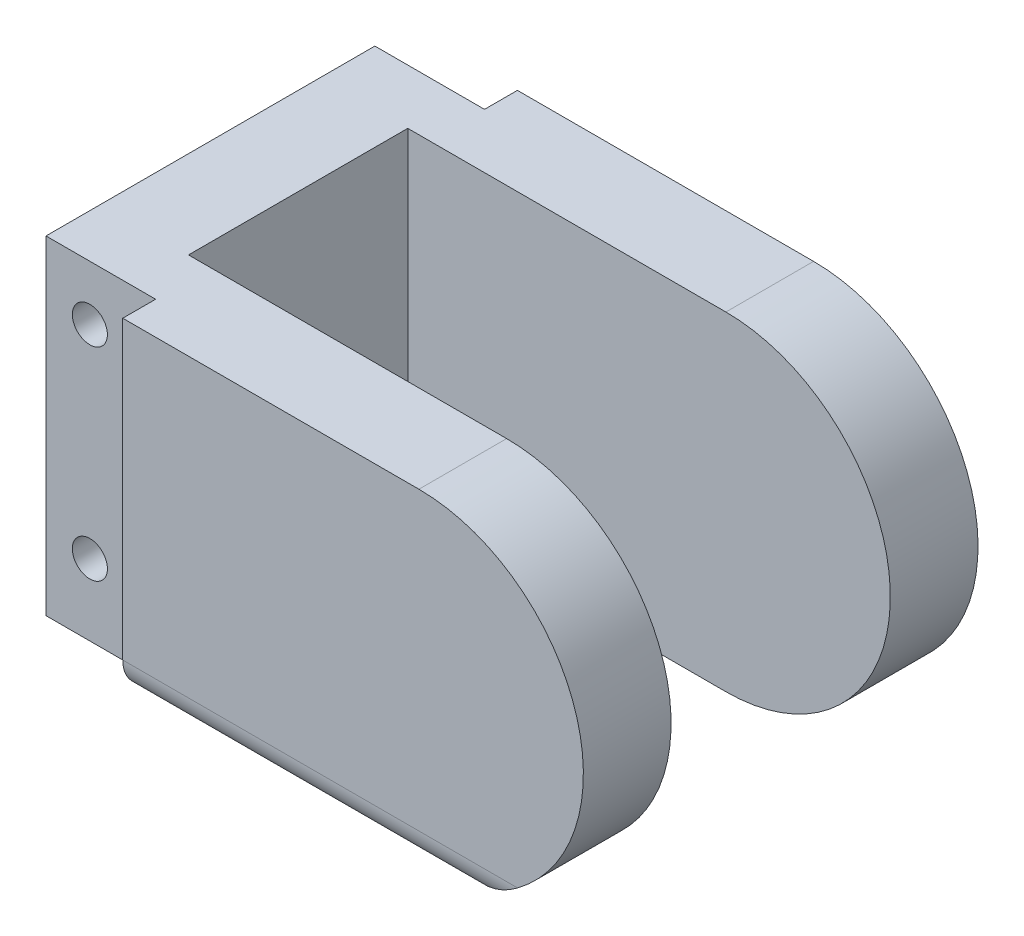
SolidWorks part; units mm, degrees
ref_plane "Front Plane" through (0, 0, 0) normal (0, 0, 1) x (1, 0, 0)
ref_plane "Top Plane" through (0, 0, 0) normal (0, 1, 0) x (1, 0, 0)
ref_plane "Right Plane" through (0, 0, 0) normal (1, 0, 0) x (0, 0, -1)
sketch "Sketch2" plane through (0, 0, -8) normal (0, 0, 1) x (1, 0, 0)
  line L0 (-25.7692, 245.1803) -> (-54.7874, 245.1803)
  line L1 (-54.7874, 245.1803) -> (-54.7874, 215.1803)
  line L2 (-54.7874, 215.1803) -> (-25.7692, 215.1803)
  arc A2 (-25.7692, 215.1803) -> (-25.7692, 245.1803) centre (-25.7692, 230.1803) ccw
  dimension "D1" = 29.0182
extrude "Boss-Extrude1" add sketch "Sketch2" along normal blind 8
sketch "Sketch3" plane through (0, 0, -28) normal (0, 0, -1) x (-1, 0, 0)
  line L3 (25.7692, 215.1803) -> (54.7874, 215.1803)
  line L4 (54.7874, 215.1803) -> (54.7874, 245.1803)
  line L5 (54.7874, 245.1803) -> (25.7692, 245.1803)
  line L6 (25.7692, 215.1803) -> (54.7874, 215.1803)
  line L7 (54.7874, 215.1803) -> (54.7874, 245.1803)
  line L8 (54.7874, 245.1803) -> (25.7692, 245.1803)
  arc A1 (25.7692, 245.1803) -> (25.7692, 215.1803) centre (25.7692, 230.1803) ccw
  arc A2 (25.7692, 245.1803) -> (25.7692, 215.1803) centre (25.7692, 230.1803) ccw
  dimension "D1" = 0
extrude "Boss-Extrude2" add sketch "Sketch3" along normal blind 8 separate body
sketch "Sketch4" plane through (-54.7874, 0, 0) normal (-1, 0, 0) x (0, 0, 1)
  line L1 (-36, 245.1803) -> (0, 245.1803)
  line L2 (-36, 245.1803) -> (-36, 215.1803)
  line L3 (-36, 215.1803) -> (0, 215.1803)
  line L4 (0, 245.1803) -> (0, 215.1803)
extrude "Boss-Extrude3" add sketch "Sketch4" along normal blind 8
sketch "Sketch7" plane through (-62.7874, 0, 0) normal (-1, 0, 0) x (0, 0, 1)
  line L0 (0, 215.1803) -> (0, 218.1803)
  line L1 (0, 215.1803) -> (0, 245.1803) construction
  line L2 (0, 215.1803) -> (-3, 215.1803)
  line L3 (-36, 215.1803) -> (0, 215.1803) construction
  line L4 (-18, 215.1803) -> (-18, 245.1803) construction
  line L5 (0, 245.1803) -> (-36, 245.1803) construction
  line L6 (-36, 215.1803) -> (-33, 215.1803)
  line L7 (-36, 215.1803) -> (-36, 218.1803)
  arc A0 (0, 218.1803) -> (-3, 215.1803) centre (-3, 218.1803) cw
  arc A1 (-36, 218.1803) -> (-33, 215.1803) centre (-33, 218.1803) ccw
extrude "Cut-Extrude2" cut sketch "Sketch7" against normal through all
sketch "Sketch8" plane through (0, 215.1803, 0) normal (0, -1, 0) x (1, 0, 0)
  line L0 (-54.7874, -8) -> (-25.7692, -8) construction
  line L1 (-56.7874, -28) -> (-39.7874, -28)
  line L2 (-56.7874, -28) -> (-56.7874, -8)
  line L3 (-56.7874, -8) -> (-39.7874, -8)
  line L4 (-39.7874, -28) -> (-39.7874, -8)
extrude "Boss-Extrude5" add sketch "Sketch8" against normal blind 7
sketch "Sketch13" plane through (0, 0, -36) normal (0, 0, -1) x (-1, 0, 0)
  line L1 (52.7874, 245.1803) -> (65.2203, 245.1803)
  line L2 (52.7874, 245.1803) -> (52.7874, 215.1803)
  line L3 (52.7874, 215.1803) -> (65.2203, 215.1803)
  line L4 (65.2203, 245.1803) -> (65.2203, 215.1803)
extrude "Cut-Extrude6" cut sketch "Sketch13" against normal blind 3
sketch "Sketch14" plane through (0, 0, 0) normal (0, 0, 1) x (1, 0, 0)
  line L4 (-52.7874, 245.1803) -> (-62.7874, 245.1803)
  line L5 (-52.7874, 215.1803) -> (-52.7874, 245.1803)
  line L6 (-62.7874, 215.1803) -> (-52.7874, 215.1803)
  line L7 (-62.7874, 245.1803) -> (-62.7874, 215.1803)
  line L8 (-52.7874, 245.1803) -> (-62.7874, 245.1803)
  line L9 (-52.7874, 215.1803) -> (-52.7874, 245.1803)
  line L10 (-62.7874, 215.1803) -> (-52.7874, 215.1803)
  line L11 (-62.7874, 245.1803) -> (-62.7874, 215.1803)
  dimension "D1" = 0
extrude "Cut-Extrude7" cut sketch "Sketch14" against normal blind 3
sketch "Sketch15" plane through (0, 0, 0) normal (0, 0, 1) x (1, 0, 0)
  spline S0 degree 3 poles (-58.7873, 241.7803) (-61.9873, 241.7803) (-61.9873, 238.5803) (-58.7873, 238.5803) (-55.5873, 238.5803) (-55.5873, 241.7803) (-58.7873, 241.7803) (-61.9873, 241.7803) (-61.9873, 238.5803) knots -0.5 0 0 0 0.5 0.5 0.5 1 1 1 1.5 1.5 1.5 weights 1 0.333333 0.333333 1 0.333333 0.333333 1 0.333333 0.333333 only from (-58.7873, 241.7803) to (-58.7873, 241.7803) construction
  spline S1 degree 3 poles (-58.7873, 223.28) (-61.9873, 223.28) (-61.9873, 220.08) (-58.7873, 220.08) (-55.5873, 220.08) (-55.5873, 223.28) (-58.7873, 223.28) (-61.9873, 223.28) (-61.9873, 220.08) knots -0.5 0 0 0 0.5 0.5 0.5 1 1 1 1.5 1.5 1.5 weights 1 0.333333 0.333333 1 0.333333 0.333333 1 0.333333 0.333333 only from (-58.7873, 223.28) to (-58.7873, 223.28) construction
  spline S2 degree 3 poles (-58.7873, 241.7803) (-61.9873, 241.7803) (-61.9873, 238.5803) (-58.7873, 238.5803) (-55.5873, 238.5803) (-55.5873, 241.7803) (-58.7873, 241.7803) (-61.9873, 241.7803) (-61.9873, 238.5803) knots -0.5 0 0 0 0.5 0.5 0.5 1 1 1 1.5 1.5 1.5 weights 1 0.333333 0.333333 1 0.333333 0.333333 1 0.333333 0.333333 only from (-58.7873, 241.7803) to (-58.7873, 241.7803)
  spline S3 degree 3 poles (-58.7873, 223.28) (-61.9873, 223.28) (-61.9873, 220.08) (-58.7873, 220.08) (-55.5873, 220.08) (-55.5873, 223.28) (-58.7873, 223.28) (-61.9873, 223.28) (-61.9873, 220.08) knots -0.5 0 0 0 0.5 0.5 0.5 1 1 1 1.5 1.5 1.5 weights 1 0.333333 0.333333 1 0.333333 0.333333 1 0.333333 0.333333 only from (-58.7873, 223.28) to (-58.7873, 223.28)
extrude "Cut-Extrude8" cut sketch "Sketch15" against normal up to surface (36 mm away) up to face at (-34.5957, 232.4912, -36)
